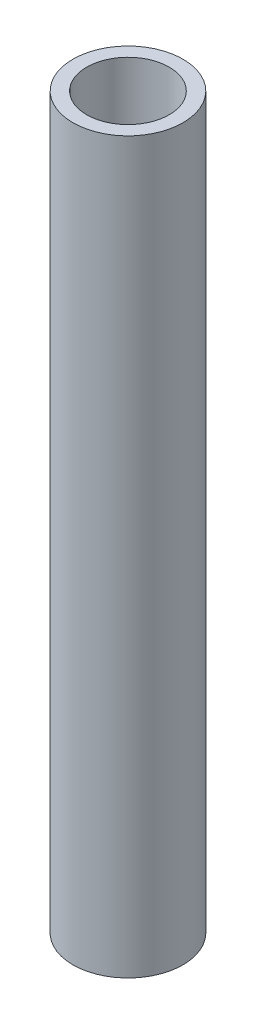
SolidWorks part; units mm, degrees
material "Brass"
ref_plane "Front Plane" through (0, 0, 0) normal (0, 0, 1) x (1, 0, 0)
ref_plane "Top Plane" through (0, 0, 0) normal (0, 1, 0) x (1, 0, 0)
ref_plane "Right Plane" through (0, 0, 0) normal (1, 0, 0) x (0, 0, -1)
sketch "Sketch1" plane through (0, 0, 0) normal (0, 1, 0) x (1, 0, 0)
  circle A0 centre (0, 0) radius 2
  circle A1 centre (0, 0) radius 1.5
  dimension "D1" = 3
  dimension "D2" = 4
extrude "Boss-Extrude1" add sketch "Sketch1" along normal blind 13.25 and the other way blind 13.25
sketch "Sketch2" plane through (0, 0, 0) normal (0, 0, 1) x (1, 0, 0)
  line L0 (2, -13.25) -> (2, 13.25) construction
  line L1 (-2, -9.7) -> (2, -9.7) construction
  line L2 (-2, -9.7) -> (-2, 9.7) construction
  line L3 (-2, 9.7) -> (2, 9.7) construction
  line L4 (2, -9.7) -> (2, 9.7) construction
  line L5 (-2, -9.7) -> (2, 9.7) construction
  line L6 (-2, 9.7) -> (2, -9.7) construction
  line L8 (2, 9.7) -> (1.75, 9.7)
  line L9 (2, 9.7) -> (2, 10.2)
  line L10 (2, 10.2) -> (1.75, 10.2)
  line L11 (1.75, 9.7) -> (1.75, 10.2)
  line L12 (0, -1000) -> (0, 49000) construction
  line L13 (2, -9.7) -> (1.75, -9.7)
  line L14 (2, -9.7) -> (2, -10.2)
  line L15 (2, -10.2) -> (1.75, -10.2)
  line L16 (1.75, -9.7) -> (1.75, -10.2)
  point P0 (0, 0)
  dimension "D1" = 0.25
  dimension "D2" = 0.5
  dimension "D3" = 19.4
revolve "Cut-Revolve1" [suppressed] cut sketch "Sketch2" angle 360 about L12
